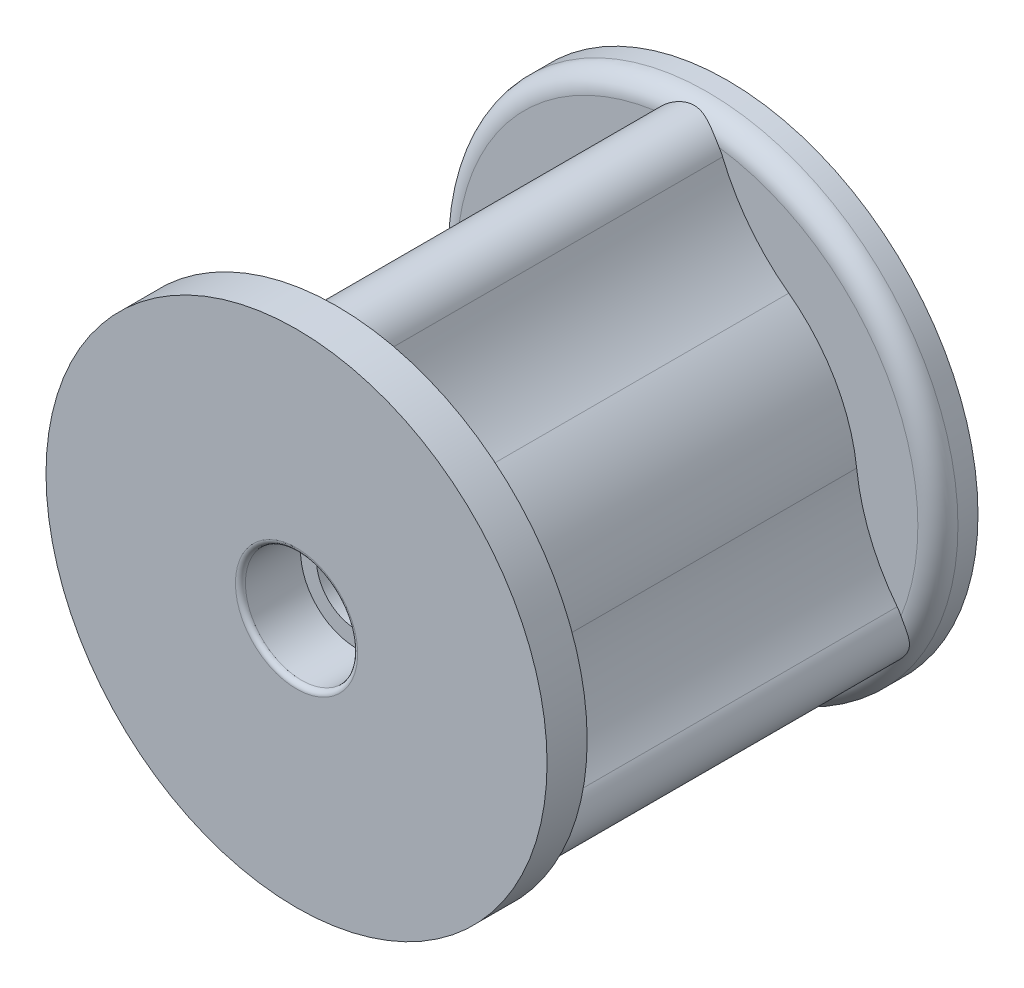
SolidWorks part; units mm, degrees
material "Plain Carbon Steel"
ref_plane "Front Plane" through (0, 0, 0) normal (1, 0, 0) x (0, 1, 0)
ref_plane "Top Plane" through (0, 0, 0) normal (0, 0, 1) x (0, 1, 0)
ref_plane "Right Plane" through (0, 0, 0) normal (0, 1, 0) x (-1, 0, 0)
sketch "Sketch1" plane through (0, 0, 0) normal (0, 0, 1) x (0, 1, 0)
  circle A0 centre (0, 0) radius 12.5
  dimension "D1" = 25
extrude "Boss-Extrude1" add sketch "Sketch1" along normal blind 2
sketch "Sketch2" plane through (0, 0, 2) normal (0, 0, 1) x (1, 0, 0)
  line L0 (0, 0) -> (0, 12.5) construction
  line L1 (0, 12.5) -> (0, 12.25) construction
  line L2 (0, 12.25) -> (0, 8.45) construction
  circle A0 centre (0, 0) radius 12.5 construction
  circle A1 centre (0, 10.35) radius 1.9
  circle A2 centre (8.9634, -5.175) radius 1.9
  circle A3 centre (-8.9634, -5.175) radius 1.9
  point P16 (0, 0)
  dimension "D3" = 3
  dimension "D1" = 0.25
  dimension "D2" = 3.8
extrude "Boss-Extrude2" add sketch "Sketch2" along normal blind 17.5
ref_plane "Plane1" through (0, 0, 10.75) normal (0, 0, 1) x (0, -1, 0)
sketch "Sketch3" plane through (0, 0, 2) normal (0, 0, 1) x (1, 0, 0)
  circle A0 centre (0, 0) radius 8.5
  dimension "D1" = 17
extrude "Boss-Extrude3" add sketch "Sketch3" along normal up to surface (8.75 mm away) up to plane "Plane1"
mirror "Mirror2" about plane through (0, 0, 10.75) normal (0, 0, 1) of "Boss-Extrude1", "Boss-Extrude3"
sketch "Sketch4" plane through (0, 0, 21.5) normal (0, 0, 1) x (1, 0, 0)
  circle A0 centre (0, 0) radius 2
  dimension "D1" = 4
extrude "Cut-Extrude1" cut sketch "Sketch4" against normal through all
sketch "Sketch5" plane through (0, 0, 0) normal (0, 0, -1) x (1, 0, 0)
  circle A0 centre (0, 0) radius 5.35
  dimension "D1" = 10.7
extrude "Cut-Extrude2" cut sketch "Sketch5" against normal blind 11.5
fillet "Fillet1" radius 0.5 1 edges at (-5.35, 0, 0)
sketch "Sketch6" plane through (0, 0, 21.5) normal (0, 0, 1) x (1, 0, 0)
  circle A0 centre (0, 0) radius 2.8
  dimension "D1" = 5.6
extrude "Cut-Extrude3" cut sketch "Sketch6" against normal blind 3
fillet "Fillet2" radius 0.25 1 edges at (2.8, 0, 21.5)
fillet "Fillet3" radius 10 1 edges at (-7.5495, -3.9057, 10.75)
fillet "Fillet4" radius 10 1 edges at (-7.1572, -4.5852, 10.75)
fillet "Fillet5" radius 10 1 edges at (0.3923, 8.4909, 10.75)
fillet "Fillet6" radius 10 1 edges at (-0.3923, 8.4909, 10.75)
fillet "Fillet7" radius 10 1 edges at (7.5495, -3.9057, 10.75)
fillet "Fillet8" radius 10 1 edges at (7.1572, -4.5852, 10.75)
fillet "Fillet9" radius 1 1 edges at (12.5, 0, 2)
fillet "Fillet10" radius 0.4 1 edges at (-5.35, 0, 11.5)
